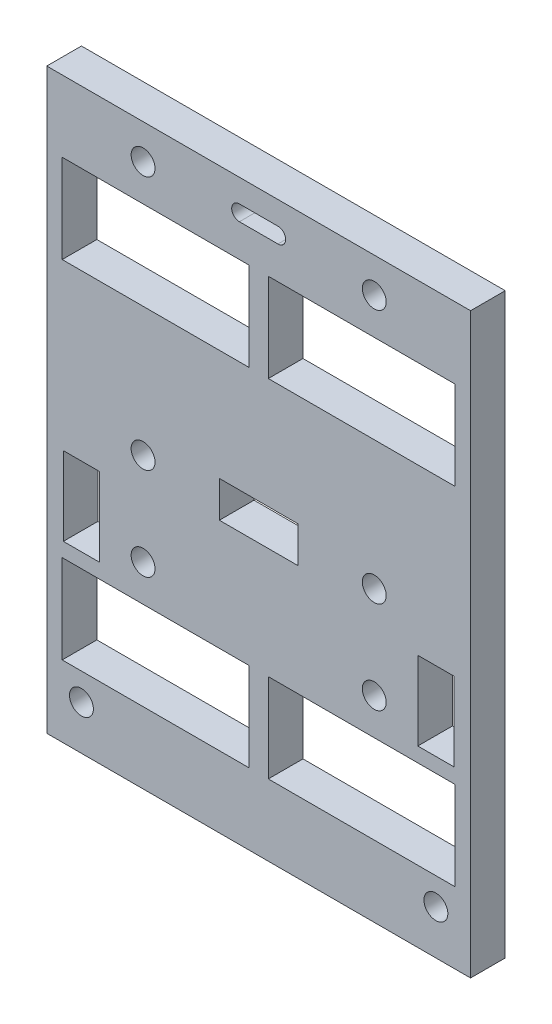
SolidWorks part; units mm, degrees
ref_plane "Front Plane" through (0, 0, 0) normal (0, 0, 1) x (1, 0, 0)
ref_plane "Top Plane" through (0, 0, 0) normal (0, 1, 0) x (1, 0, 0)
ref_plane "Right Plane" through (0, 0, 0) normal (1, 0, 0) x (0, 0, -1)
sketch "Sketch1" plane through (0, 0, 0) normal (0, 0, 1) x (1, 0, 0)
  line L0 (0, -37.5) -> (0, 37.5) construction
  line L1 (-27.5, -37.5) -> (27.5, -37.5)
  line L2 (-27.5, -37.5) -> (-27.5, 37.5)
  line L3 (-27.5, 37.5) -> (27.5, 37.5)
  line L4 (27.5, -37.5) -> (27.5, 37.5)
  line L5 (-27.5, -37.5) -> (27.5, 37.5) construction
  line L6 (-27.5, 37.5) -> (27.5, -37.5) construction
  line L7 (-27.5, 0) -> (27.5, 0) construction
  line L8 (-27.5, 22.5) -> (27.5, 22.5) construction
  line L9 (25.5, 16.75) -> (1.25, 28.25) construction
  line L10 (-25.5, 28.25) -> (-1.25, 28.25)
  line L11 (-25.5, 28.25) -> (-25.5, 16.75)
  line L12 (-25.5, 16.75) -> (-1.25, 16.75)
  line L13 (-1.25, 28.25) -> (-1.25, 16.75)
  line L14 (-25.5, 28.25) -> (-1.25, 16.75) construction
  line L15 (-25.5, 16.75) -> (-1.25, 28.25) construction
  line L16 (25.5, 28.25) -> (1.25, 16.75) construction
  line L17 (1.25, 28.25) -> (1.25, 16.75)
  line L18 (25.5, 16.75) -> (1.25, 16.75)
  line L19 (25.5, 28.25) -> (25.5, 16.75)
  line L20 (25.5, 28.25) -> (1.25, 28.25)
  line L21 (25.5, -28.25) -> (1.25, -16.75) construction
  line L22 (-25.5, -16.75) -> (-1.25, -28.25) construction
  line L23 (-25.5, -28.25) -> (-1.25, -16.75) construction
  line L24 (25.5, -16.75) -> (1.25, -28.25) construction
  line L25 (25.5, -28.25) -> (1.25, -28.25)
  line L26 (25.5, -28.25) -> (25.5, -16.75)
  line L27 (25.5, -16.75) -> (1.25, -16.75)
  line L28 (1.25, -28.25) -> (1.25, -16.75)
  line L29 (-1.25, -28.25) -> (-1.25, -16.75)
  line L30 (-25.5, -16.75) -> (-1.25, -16.75)
  line L31 (-25.5, -28.25) -> (-25.5, -16.75)
  line L32 (-25.5, -28.25) -> (-1.25, -28.25)
  point P0 (0, 0)
  point P12 (-13.375, 22.5)
  point P21 (13.375, 22.5)
  point P30 (13.375, -22.5)
  point P31 (-13.375, -22.5)
  dimension "D1" = 55
  dimension "D2" = 75
  dimension "D3" = 22.5
  dimension "D4" = 24.25
  dimension "D5" = 11.5
  dimension "D6" = 1.25
extrude "Boss-Extrude1" add sketch "Sketch1" along normal blind 4.5
sketch "Sketch2" plane through (0, 0, 4.5) normal (0, 0, 1) x (1, 0, 0)
  line L0 (0, -37.5) -> (0, 37.5) construction
  line L1 (-27.5, -37.5) -> (27.5, -37.5) construction
  line L2 (27.5, 37.5) -> (-27.5, 37.5) construction
  line L3 (-27.5, 0) -> (27.5, 0) construction
  line L4 (-27.5, 37.5) -> (-27.5, -37.5) construction
  line L5 (27.5, -37.5) -> (27.5, 37.5) construction
  line L6 (-15, 0) -> (15, 0) construction
  circle A0 centre (-15, 33) radius 1.55
  circle A1 centre (15, 33) radius 1.55
  circle A2 centre (15, 0) radius 1.55
  circle A3 centre (-15, 0) radius 1.55
  dimension "D1" = 3.1
  dimension "D7" = 3.1
  dimension "D8" = 3.1
  dimension "D2" = 15
  dimension "D3" = 33
  dimension "D4" = 30
  dimension "D5" = 15
  dimension "D6" = 0
extrude "screwHoles" cut sketch "Sketch2" against normal through all
sketch "Sketch3" plane through (0, 0, 4.5) normal (0, 0, 1) x (1, 0, 0)
  line L0 (-27.5, 9) -> (26.0486, 9) construction
  line L1 (-27.5, 37.5) -> (-27.5, -37.5) construction
  line L3 (0, 37.5) -> (0, -37.5) construction
  line L4 (27.5, 37.5) -> (-27.5, 37.5) construction
  line L5 (-27.5, -37.5) -> (27.5, -37.5) construction
  line L6 (19.1, 6.65) -> (8.9, 11.35) construction
  line L7 (-19.1, 11.35) -> (-8.9, 11.35)
  line L8 (-19.1, 11.35) -> (-19.1, 6.65)
  line L9 (-19.1, 6.65) -> (-8.9, 6.65)
  line L10 (-8.9, 11.35) -> (-8.9, 6.65)
  line L11 (-19.1, 11.35) -> (-8.9, 6.65) construction
  line L12 (-19.1, 6.65) -> (-8.9, 11.35) construction
  line L13 (19.1, 11.35) -> (8.9, 6.65) construction
  line L14 (8.9, 11.35) -> (8.9, 6.65)
  line L15 (19.1, 6.65) -> (8.9, 6.65)
  line L16 (19.1, 11.35) -> (19.1, 6.65)
  line L17 (19.1, 11.35) -> (8.9, 11.35)
  line L18 (-27.5, 37.5) -> (-27.5, -37.5) construction
  point P2 (-27.5, 0)
  point P12 (-14, 9)
  point P21 (14, 9)
  dimension "D1" = 10.2
  dimension "D2" = 4.7
  dimension "D3" = 14
  dimension "D4" = 9
extrude "BeltClamp" [suppressed] cut sketch "Sketch3" against normal through all
sketch "Sketch4" plane through (0, 0, 4.5) normal (0, 0, 1) x (1, 0, 0)
  line L0 (-27.5, 0) -> (27.5, 0) construction
  line L1 (-27.5, 37.5) -> (-27.5, -37.5) construction
  line L2 (27.5, -37.5) -> (27.5, 37.5) construction
  line L4 (-5.1, 2.35) -> (5.1, 2.35)
  line L5 (-5.1, 2.35) -> (-5.1, -2.35)
  line L6 (-5.1, -2.35) -> (5.1, -2.35)
  line L7 (5.1, 2.35) -> (5.1, -2.35)
  line L8 (-5.1, 2.35) -> (5.1, -2.35) construction
  line L9 (-5.1, -2.35) -> (5.1, 2.35) construction
  circle A0 centre (-15, 0) radius 1.55 construction
  point P6 (0, 0)
  dimension "D1" = 10.2
  dimension "D2" = 4.7
  dimension "D3" = 0
extrude "mountingPlateTab" cut sketch "Sketch4" against normal through all
sketch "Sketch5" plane through (0, 0, 4.5) normal (0, 0, 1) x (1, 0, 0)
  line L0 (-27.5, -9.75) -> (27.5, -9.75) construction
  line L1 (-27.5, 37.5) -> (-27.5, -37.5) construction
  line L2 (27.5, -37.5) -> (27.5, 37.5) construction
  line L4 (0, -37.5) -> (0, 37.5) construction
  line L5 (-27.5, -37.5) -> (27.5, -37.5) construction
  line L6 (27.5, 37.5) -> (-27.5, 37.5) construction
  line L7 (-20.65, -14.85) -> (-25.35, -4.65) construction
  line L8 (20.65, -4.65) -> (25.35, -4.65)
  line L9 (20.65, -4.65) -> (20.65, -14.85)
  line L10 (20.65, -14.85) -> (25.35, -14.85)
  line L11 (25.35, -4.65) -> (25.35, -14.85)
  line L12 (20.65, -4.65) -> (25.35, -14.85) construction
  line L13 (20.65, -14.85) -> (25.35, -4.65) construction
  line L14 (-20.65, -4.65) -> (-25.35, -14.85) construction
  line L15 (-25.35, -4.65) -> (-25.35, -14.85)
  line L16 (-20.65, -14.85) -> (-25.35, -14.85)
  line L17 (-20.65, -4.65) -> (-20.65, -14.85)
  line L18 (-20.65, -4.65) -> (-25.35, -4.65)
  line L19 (23, -9.75) -> (23, -37.5) construction
  line L20 (-23, -9.75) -> (-23, -37.5) construction
  circle A0 centre (23, -31.75) radius 1.55
  circle A1 centre (-23, -31.75) radius 1.55
  point P15 (23, -9.75)
  point P24 (-23, -9.75)
  dimension "D5" = 3.1
  dimension "D2" = 10.2
  dimension "D3" = 4.7
  dimension "D4" = 23
  dimension "D6" = 22
  dimension "D1" = 9.75
extrude "BraceTabs" cut sketch "Sketch5" against normal through all
sketch "Sketch6" plane through (0, 0, 4.5) normal (0, 0, 1) x (1, 0, 0)
  line L0 (-25.35, -9.75) -> (25.35, -9.75) construction
  line L1 (-25.35, -4.65) -> (-25.35, -14.85) construction
  line L2 (25.35, -14.85) -> (25.35, -4.65) construction
  line L3 (0, -2.35) -> (0, -37.5) construction
  line L4 (-5.1, -2.35) -> (5.1, -2.35) construction
  line L5 (-27.5, -37.5) -> (27.5, -37.5) construction
  line L6 (23, -14.85) -> (23, -4.65) construction
  line L7 (20.65, -14.85) -> (25.35, -14.85) construction
  line L8 (25.35, -4.65) -> (20.65, -4.65) construction
  line L9 (20.65, -4.65) -> (20.65, -14.85) construction
  line L10 (19.65, -15.85) -> (26.35, -15.85)
  line L11 (19.65, -15.85) -> (19.65, -3.65)
  line L12 (19.65, -3.65) -> (26.35, -3.65)
  line L13 (26.35, -15.85) -> (26.35, -3.65)
  line L14 (19.65, -15.85) -> (26.35, -3.65) construction
  line L15 (19.65, -3.65) -> (26.35, -15.85) construction
  line L16 (-19.65, -3.65) -> (-26.35, -15.85) construction
  line L17 (-19.65, -15.85) -> (-26.35, -3.65) construction
  line L18 (-23, -14.85) -> (-23, -4.65) construction
  line L19 (-26.35, -15.85) -> (-26.35, -3.65)
  line L20 (-19.65, -3.65) -> (-26.35, -3.65)
  line L21 (-19.65, -15.85) -> (-19.65, -3.65)
  line L22 (-19.65, -15.85) -> (-26.35, -15.85)
  circle A0 centre (23, -9.75) radius 1.55
  circle A1 centre (-23, -9.75) radius 1.55
  point P18 (23, -9.75)
  dimension "D3" = 3.1
  dimension "D1" = 1
  dimension "D2" = 1
extrude "FrontToRear1" [suppressed] add sketch "Sketch6" against normal up to surface (4.5 mm away) up to face at (-24.55, -31.75, 0)
sketch "Sketch7" plane through (0, 0, 4.5) normal (0, 0, 1) x (1, 0, 0)
  line L0 (5.1, 2.35) -> (-5.1, 2.35) construction
  line L1 (-20, -3.35) -> (20, -3.35)
  line L2 (-20, -3.35) -> (-20, 3.35)
  line L3 (-20, 3.35) -> (20, 3.35)
  line L4 (20, -3.35) -> (20, 3.35)
  line L5 (-20, -3.35) -> (20, 3.35) construction
  line L6 (-20, 3.35) -> (20, -3.35) construction
  circle A0 centre (15, 0) radius 1.55 construction
  point P0 (0, 0)
  dimension "D1" = 1
  dimension "D2" = 5
extrude "FrontToRear2" [suppressed] add sketch "Sketch7" against normal through all
sketch "Sketch8" plane through (0, 0, 4.5) normal (0, 0, 1) x (1, 0, 0)
  line L0 (-27.5, -12) -> (27.5, -12) construction
  line L1 (-27.5, 37.5) -> (-27.5, -37.5) construction
  line L2 (27.5, -37.5) -> (27.5, 37.5) construction
  line L3 (0, -37.5) -> (0, 0) construction
  line L4 (-27.5, -37.5) -> (27.5, -37.5) construction
  circle A0 centre (-15, -12) radius 1.55
  circle A1 centre (15, -12) radius 1.55
  dimension "D2" = 3.1
  dimension "D1" = 12
  dimension "D3" = 15
extrude "ExpansionScrewholes" cut sketch "Sketch8" against normal through all
sketch "Sketch12" plane through (0, 0, 4.5) normal (0, 0, 1) x (1, 0, 0)
  line L0 (0, 37.5) -> (0, 0) construction
  line L1 (27.5, 37.5) -> (-27.5, 37.5) construction
  line L2 (-2.5, 33.5) -> (2.5, 33.5) construction
  line L3 (-2.5, 34.5) -> (2.5, 34.5)
  line L4 (-2.5, 32.5) -> (2.5, 32.5)
  arc A0 (-2.5, 34.5) -> (-2.5, 32.5) centre (-2.5, 33.5) ccw
  arc A1 (2.5, 32.5) -> (2.5, 34.5) centre (2.5, 33.5) ccw
  point P7 (0, 33.5)
  dimension "D1" = 3
  dimension "D2" = 2
  dimension "D3" = 5
extrude "CableTieSlot" cut sketch "Sketch12" against normal through all
sketch "Sketch11" [suppressed] plane through (0, 0, 4.5) normal (0, 0, 1) x (1, 0, 0)
  line L0 (13.5615, -8.85) -> (27.5, -8.85) construction
  line L1 (27.5, -37.5) -> (27.5, 37.5) construction
  line L2 (0, 37.5) -> (0, -37.5) construction
  line L3 (36.5, -14.85) -> (18.5, -14.85)
  line L4 (36.5, -14.85) -> (36.5, -2.85)
  line L5 (36.5, -2.85) -> (18.5, -2.85)
  line L6 (18.5, -14.85) -> (18.5, -2.85)
  line L7 (36.5, -14.85) -> (18.5, -2.85) construction
  line L8 (36.5, -2.85) -> (18.5, -14.85) construction
  line L11 (-36.5, -2.85) -> (-18.5, -14.85) construction
  line L12 (-36.5, -14.85) -> (-18.5, -2.85) construction
  line L13 (-18.5, -14.85) -> (-18.5, -2.85)
  line L14 (-36.5, -2.85) -> (-18.5, -2.85)
  line L15 (-36.5, -14.85) -> (-36.5, -2.85)
  line L16 (-36.5, -14.85) -> (-18.5, -14.85)
  line L17 (36.5, -2.85) -> (18.5, -14.85) construction
  line L18 (20.65, -14.85) -> (25.35, -14.85) construction
  line L19 (27.5, 37.5) -> (-27.5, 37.5) construction
  line L20 (-27.5, -37.5) -> (27.5, -37.5) construction
  dimension "D1" = 9
  dimension "D2" = 12
  dimension "D3" = 0
extrude "Cut-Extrude2" [suppressed] cut sketch "Sketch11" against normal through all
sketch "Sketch10" plane through (0, 0, 4.5) normal (0, 0, 1) x (1, 0, 0)
  line L0 (4.7446, 1) -> (27.5, 1) construction
  line L1 (-5.1, 0) -> (5.1, 0) construction
  line L2 (27.5, -37.5) -> (27.5, 37.5) construction
  line L3 (0, 2.35) -> (0, -2.35) construction
  line L4 (36.5, 4) -> (18.5, 4)
  line L5 (36.5, 4) -> (36.5, -2)
  line L6 (36.5, -2) -> (18.5, -2)
  line L7 (18.5, 4) -> (18.5, -2)
  line L8 (36.5, 4) -> (18.5, -2) construction
  line L9 (36.5, -2) -> (18.5, 4) construction
  line L10 (5.1, 2.35) -> (-5.1, 2.35) construction
  line L11 (-5.1, -2.35) -> (5.1, -2.35) construction
  line L12 (-36.5, -2) -> (-18.5, 4) construction
  line L13 (-36.5, 4) -> (-18.5, -2) construction
  line L14 (-4.7446, 1) -> (-27.5, 1) construction
  line L15 (-18.5, 4) -> (-18.5, -2)
  line L16 (-36.5, -2) -> (-18.5, -2)
  line L17 (-36.5, 4) -> (-36.5, -2)
  line L18 (-36.5, 4) -> (-18.5, 4)
  line L19 (36.5, -2) -> (18.5, 4) construction
  line L20 (-5.1, 2.35) -> (-5.1, -2.35) construction
  line L21 (5.1, -2.35) -> (5.1, 2.35) construction
  dimension "D1" = 6
  dimension "D2" = 9
  dimension "D3" = 1
extrude "CableTieSlots" [suppressed] cut sketch "Sketch10" against normal through all
sketch "Sketch9" [suppressed] plane through (0, 0, 4.5) normal (0, 0, 1) x (1, 0, 0)
  line L0 (-27.5, -37.5) -> (27.5, -37.5) construction
  line L5 (-9, -42.5) -> (9, -42.5)
  line L6 (-9, -42.5) -> (-9, -34.5)
  line L7 (-7, -32.5) -> (7, -32.5)
  line L8 (9, -42.5) -> (9, -34.5)
  line L9 (-9, -42.5) -> (9, -32.5) construction
  line L10 (-9, -32.5) -> (9, -42.5) construction
  arc A0 (7, -32.5) -> (9, -34.5) centre (7, -34.5) cw
  arc A1 (-9, -34.5) -> (-7, -32.5) centre (-7, -34.5) cw
  point P9 (0, -37.5)
  line M42 (-27.5, -37.5) -> (27.5, -37.5)
  dimension "D3" = 2
  dimension "D1" = 18
  dimension "D2" = 5
extrude "RearFanSlot" [suppressed] cut sketch "Sketch9" against normal through all contours A1 L6 L8 A0 L7 M42 | L5 L8 L6 M42
sketch "Sketch13" [suppressed] plane through (0, 0, 4.5) normal (0, 0, 1) x (1, 0, 0)
  line L1 (-7, -2.85) -> (7, -2.85)
  line L2 (-7, -2.85) -> (-7, -11.85)
  line L3 (-7, -11.85) -> (7, -11.85)
  line L4 (7, -2.85) -> (7, -11.85)
  line L5 (-7, -2.85) -> (7, -11.85) construction
  line L6 (-7, -11.85) -> (7, -2.85) construction
  line L9 (0, 37.5) -> (0, -7.35) construction
  line L10 (-18.5, -2.85) -> (-27.5, -2.85) construction
  line L11 (27.5, 37.5) -> (-27.5, 37.5) construction
  line L13 (-27.5, -14.85) -> (-18.5, -14.85) construction
  point P0 (0, -7.35)
  dimension "D1" = 3
  dimension "D2" = 0
  dimension "D3" = 7
extrude "Cut-Extrude3" [suppressed] cut sketch "Sketch13" against normal through all
equation "\"X-ROD-SPACING\"=45"
equation "\"Y-ROD-SPACING\"=75"
equation "\"Z-ROD-SPACING\"=17.5"
equation "\"Y-BED-OFFSET\"=2"
equation "\"Y-BED-ROD-INSET\"=3.5"
equation "\"Y-BED-SCREW-SPACING\"=209"
equation "\"Y-BED-SCREW-CUTOUT-SLOT-HEIGHT\"=2"
equation "\"T-SLOT-NUT-FILLET-RADIUS\"=0.25"
equation "\"T-SLOT-SCREW-SHAFT-RADIUS\"=1.75"
equation "\"T-SLOT-SCREW-SHAFT-CUTOUT-LENGTH\"=10.5"
equation "\"T-SLOT-NUT-DEPTH\"=4.2"
equation "\"T-SLOT-NUT-WIDTH\"=3"
equation "\"T-SLOT-NUT-END-DISTANCE\"=8"
equation "\"ACRYLIC-THICKNESS\"=10"
equation "\"ACRYLIC-THICKNESS2\"=4.5"
equation "\"ACRYLIC-TAB-CUTOUT-SIZE\"=\"ACRYLIC-THICKNESS\"+\"ACRYLIC-TAB-TOLERANCE\"*2"
equation "\"ACRYLIC-TAB-WIDTH\"=\"ACRYLIC-THICKNESS\""
equation "\"ACRYLIC-M3-HOLE\"=3.1"
equation "\"SMOOTHROD-CAP-SCREW-DISTANCE\"=20"
equation "\"FRAME-WIDTH-INNER\"=370"
equation "\"NEMA17-HOLE-SPACING\"=31"
equation "\"NEMA17-CENTRAL-CUTOUT\"=22.5"
equation "\"Z-BRACKET-REACH\"=55"
equation "\"Z-ROD-INSET\"=16"
equation "\"TOP-BRACKET-SPACING\"=40"
equation "\"SMOOTHROD-X-LENGTH\"=350"
equation "\"SMOOTHROD-Y-LENGTH\"=350"
equation "\"SMOOTHROD-Z-LENGTH\"=350"
equation "\"SMOOTHROD-TIGHTENING-HEADROOM\"=.25"
equation "\"LEADSCREW-Z-LENGTH\"=300"
equation "\"SCREW-LENGTH-FRAME\"=\"ACRYLIC-THICKNESS\" + 10"
equation "\"SCREW-LENGTH-MOTOR\"=\"ACRYLIC-THICKNESS\" + 5"
equation "\"SCREW-HEAD-RADIUS\"=6"
equation "\"PRINTED-X-SMOOTHROD-DIAMETER\"=8.2"
equation "\"PRINTED-X-SMOOTHROD-CUTOUT\"=10"
equation "\"PRINTED-X-BASE-HEIGHT\"=10"
equation "\"PRINTED-LM8UU-CUTOUT-SIZE\"=15.25"
equation "\"PRINTED-LM8UU-CUTOUT-LENGTH\"=24.5"
equation "\"PRINTED-X-IDLER-HEIGHT\"=16"
equation "\"PSU-MOUNTING-WIDTH\"=95"
equation "\"PSU-MOUNTING-HEIGHT\"=177"
equation "\"Y-BELT-TO-ROD-DISTANCE\"=20"
equation "\"SPOOL-HOLDER-ROD-SPACING\"=150"
equation "\"D3@Sketch1\"=\"X-ROD-SPACING\"/2"
equation "\"D4@Sketch1\"=\"ACRYLIC-X-CARRIAGE-LM8UU-CUTOUT-WIDTH\""
equation "\"D1@Boss-Extrude1\"=\"ACRYLIC-THICKNESS2\""
equation "\"D1@Sketch2\"=\"ACRYLIC-M3-HOLE\""
equation "\"D1@Sketch3\"=\"ACRYLIC-TAB-CUTOUT-SIZE\""
equation "\"D2@Sketch3\"=\"ACRYLIC-THICKNESS2\"+\"ACRYLIC-TAB-TOLERANCE\"*2"
equation "\"ACRYLIC-X-CARRIAGE-WIDTH\"=55"
equation "\"ACRYLIC-X-CARRIAGE-HEIGHT\"=75"
equation "\"D1@Sketch1\"=\"ACRYLIC-X-CARRIAGE-WIDTH\""
equation "\"D2@Sketch1\"=\"ACRYLIC-X-CARRIAGE-HEIGHT\""
equation "\"ACRYLIC-X-CARRIAGE-CENTER-TAB-SPACING\"=14"
equation "\"D3@Sketch3\"=\"ACRYLIC-X-CARRIAGE-CENTER-TAB-SPACING\""
equation "\"SCREW-LENGTH-EXTRUDER\"=28"
equation "\"ACRYLIC-X-CARRIAGE-SCREW-SPACING-X\"=15"
equation "\"ACRYLIC-X-CARRIAGE-SCREW-SPACING-Y\"=33"
equation "\"D2@Sketch2\"=\"ACRYLIC-X-CARRIAGE-SCREW-SPACING-X\""
equation "\"D3@Sketch2\"=\"ACRYLIC-X-CARRIAGE-SCREW-SPACING-Y\""
equation "\"D1@Sketch4\"=\"ACRYLIC-TAB-CUTOUT-SIZE\""
equation "\"D2@Sketch4\"=\"ACRYLIC-THICKNESS2\"+\"ACRYLIC-TAB-TOLERANCE\"*2"
equation "\"D2@Sketch5\"=\"ACRYLIC-TAB-CUTOUT-SIZE\""
equation "\"D3@Sketch5\"=\"ACRYLIC-THICKNESS2\"+\"ACRYLIC-TAB-TOLERANCE\"*2"
equation "\"ACRYLIC-X-CARRIAGE-EXTRUDER-SHELF-DEPTH\"=\"ACRYLIC-X-CARRIAGE-EXTRUDER-OFFSET\" + 28"
equation "\"ACRYLIC-X-CARRIAGE-EXTRUDER-BRACE-SPACING\"=23"
equation "\"D4@Sketch5\"=\"ACRYLIC-X-CARRIAGE-EXTRUDER-BRACE-SPACING\""
equation "\"D4@Sketch2\"=\"ACRYLIC-X-CARRIAGE-SCREW-SPACING-X\"*2"
equation "\"D5@Sketch2\"=\"ACRYLIC-X-CARRIAGE-SCREW-SPACING-X\""
equation "\"D7@Sketch2\"=\"ACRYLIC-M3-HOLE\""
equation "\"D8@Sketch2\"=\"ACRYLIC-M3-HOLE\""
equation "\"ACRYLIC-X-CARRIAGE-LM8UU-CUTOUT-WIDTH\"=24.25"
equation "\"ACRYLIC-TAB-TOLERANCE\"=.1"
equation "\"ACRYLIC-X-CARRIAGE-EXTRUDER-OFFSET\"=26"
equation "\"ACRYLIC-X-CARRIAGE-EXTRUDER-ANGLE\"=90"
equation "\"ACRYLIC-X-CARRIAGE-EXTRUDER-BRACE-TAB-OFFSET\"=20"
equation "\"ACRYLIC-X-CARRIAGE-EXTRUDER-BRACE-HEIGHT\"=35"
equation "\"ACRYLIC-X-CARRIAGE-EXTRUDER-BRACE-SCREW-SPACING\"=22"
equation "\"D5@Sketch5\"=\"ACRYLIC-M3-HOLE\""
equation "\"D3@Sketch6\"=\"ACRYLIC-M3-HOLE\""
equation "\"ACRYLIC-X-CARRIAGE-LM8UU-CUTOUT-HEIGHT\"=11.5"
equation "\"ACRYLIC-X-CARRIAGE-DUAL-WIDTH-MULTIPLIER\"=1.65"
equation "\"ACRYLIC-X-CARRIAGE-DUAL-HOTEND-SPACING\"=42"
equation "\"ACRYLIC-X-CARRIAGE-DUAL-WIDTH\"=95"
equation "\"ACRYLIC-X-CARRIAGE-DUAL-HOTEND-SEPARATION\"=35"
equation "\"ACRYLIC-X-CARRIAGE-DUAL-MOUNT-PLATE-DEPTH\"=75"
equation "\"ACRYLIC-X-CARRIAGE-DUAL-MOUNT-BRACE-WIDTH\"=33"
equation "\"ACRYLIC-X-CARRIAGE-DUAL-MOUNT-SCREW-WIDTH\"=40"
equation "\"D5@Sketch1\"=\"ACRYLIC-X-CARRIAGE-LM8UU-CUTOUT-HEIGHT\""
equation "\"D2@Sketch8\"=\"ACRYLIC-M3-HOLE\""
equation "\"D1@Sketch5\"=\"ACRYLIC-THICKNESS2\"/2 + 7.5"
